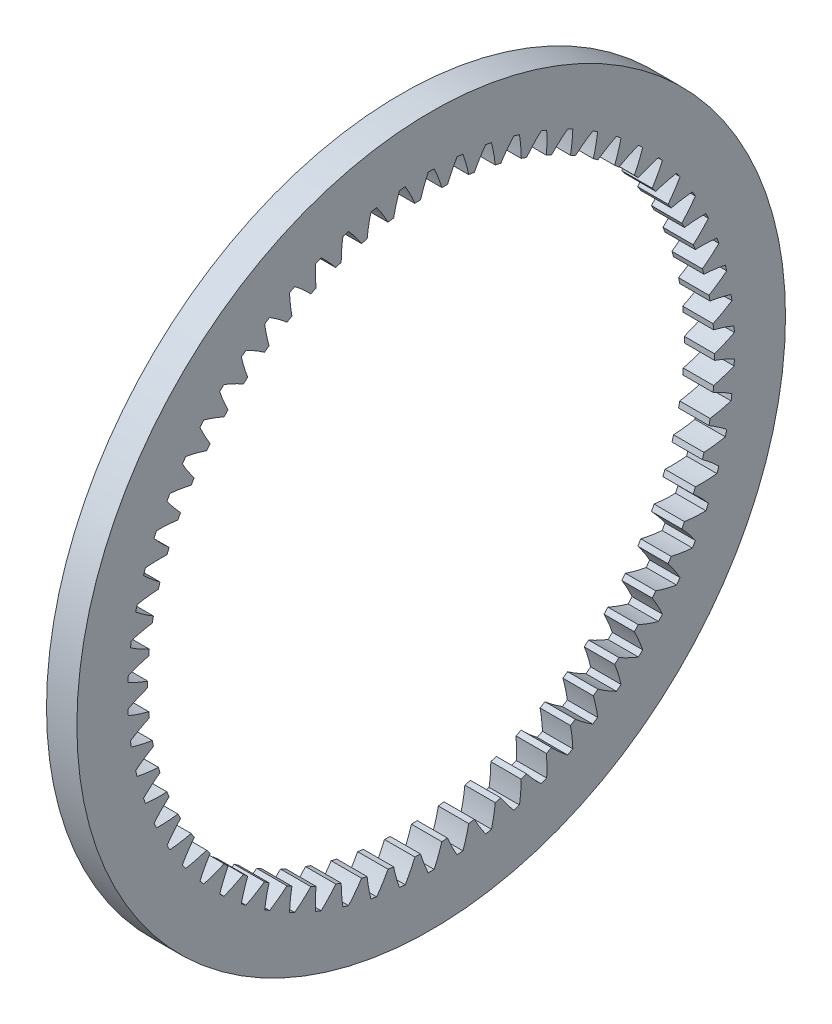
SolidWorks part; units mm, degrees
ref_plane "Plane1" through (0, 0, 0) normal (0, 0, 1) x (1, 0, 0)
ref_plane "Plane2" through (0, 0, 0) normal (0, 1, 0) x (1, 0, 0)
ref_plane "Plane3" through (0, 0, 0) normal (1, 0, 0) x (0, 0, -1)
other "Configuration Table"
sketch "HoldingSke" plane through (0, 0, 0) normal (0, 1, 0) x (1, 0, 0)
  line L0 (0, 0) -> (0.2324, -0.522)
  line L1 (-15, 0) -> (100, 0) construction
  line L2 (0, 0) -> (-2.1039, 2.3779)
  line L3 (0, 0) -> (-11.863, 4.5341)
  line L4 (0, 0) -> (3.5126, 7.8894)
  line L5 (0, 0) -> (-23.7986, -8.8762)
  line L6 (0, 0) -> (-10.5278, -7.1032)
  line L7 (-2.1039, 2.3779) -> (3.3635, 27.1825)
  line L8 (-76.2, 4.1279) -> (-54.61, 4.1279)
  line L9 (-71.009, 38.7566) -> (-53.1078, 45.2721)
  line L10 (-76.2, 71.12) -> (104.1128, 71.12)
  line L11 (0, 0) -> (-6, 0)
  line L12 (-76.2, 101.6) -> (-76.147, 101.6)
  line L13 (24.9733, 27.94) -> (52.9518, 28.4284)
  line L14 (24.9733, 27.94) -> (24.9743, 27.94)
  line L15 (24.9733, 27.94) -> (100.4006, 29.5858)
  circle A0 centre (0, 0) radius 70
  circle A1 centre (0, 0) radius 12.7
  circle A2 centre (0, 0) radius 12.7
  dimension "Num_teeth" = 66
  dimension "Pitch_radius" = 180.3128
  dimension "Width" = 6
  dimension "Diameter" = 140
sketch "BasProSke" plane through (0, 0, 0) normal (0, 1, 0) x (1, 0, 0)
  line L0 (-10, 0) -> (60, 0) construction
  line L1 (0, 56) -> (0, 70)
  line L2 (0, 56) -> (6, 56)
  line L3 (6, 56) -> (6, 70)
  line L4 (6, 70) -> (0, 70)
  dimension "Thickness" = 6
  dimension "Diameter" = 140
revolve "Base-Revolve" add sketch "BasProSke" angle 360 about L0
sketch "TooCutSke" plane through (0, 0, 0) normal (1, 0, 0) x (0, 0, -1)
  line L3 (1.5068, 57.7303) -> (1.5068, 53.6633) construction
  line L4 (0, 0) -> (0, 59.563) construction
  line L5 (0, 0) -> (-3.2512, 68.2501) construction
  line L6 (-25.562, 47.6782) -> (35.476, 50.5858) construction
  circle A0 centre (0, 0) radius 57.75 construction
  circle A1 centre (0, 0) radius 59.9385 construction
  circle A2 centre (0, 0) radius 48.8405 construction
  circle A3 centre (0, 0) radius 55.9746 construction
  arc A4 (2.1073, 55.9349) -> (0.5822, 59.9357) centre (-25.562, 47.6782) ccw
  arc A5 (2.1073, 55.9349) -> (-2.1073, 55.9349) centre (0, 0) ccw
  arc A6 (0.5822, 59.9357) -> (-0.5822, 59.9357) centre (0, 0) ccw
  arc A7 (-0.5822, 59.9357) -> (-2.1073, 55.9349) centre (25.562, 47.6782) ccw
extrude "ToothCut" cut sketch "TooCutSke" along normal through all
fillet "Breaks" [suppressed] radius 0.175
fillet "RootFillets" [suppressed] radius 0.4385
pattern_circular "TeethCuts" count 66 every 5.455 about axis through (-10, 0, 0) along (1, 0, 0) of "RootFillets", "Breaks", "ToothCut"
equation "' \"Module@HoldingSke\" = 6.35"
equation "' \"Num_teeth@HoldingSke\" = 24"
equation "' \"Ap@HoldingSke\" =  14.5"
equation "' \"Ap@HoldingSke\" = 14.5"
equation "' \"Width@HoldingSke\" = 12"
equation "' \"Diameter@HoldingSke\" = 8 * 25.4"
equation "' \"Show_teeth@HoldingSke\" = 100"
equation "' \"Backlash@HoldingSke\" = 0.009 * 25.4"
equation "' \"Addendum_fac@HoldingSke\" = 1.0"
equation "' \"Dedendum_fac@HoldingSke\" = 1.25"
equation "' \"Dedendum_add@HoldingSke\" = 0.00005 * 25.4"
equation "' \"Clearance_fac@HoldingSke\" = 0.25"
equation "\"Pitch@HoldingSke\" = 1 / \"Module@HoldingSke\" "
equation "\"Overcut_dia@TooCutSke\" = (\"Num_teeth@HoldingSke\" - 2 * \"Addendum_fac@HoldingSke\") / \"Pitch@HoldingSke\" - 0.002 * 25.4"
equation "\"Pitch_dia@TooCutSke\" = \"Num_teeth@HoldingSke\" / \"Pitch@HoldingSke\""
equation "\"Base_dia@TooCutSke\" = \"Num_teeth@HoldingSke\" / \"Pitch@HoldingSke\" * cos((\"Ap@HoldingSke\"  * 3.14159265 / 180)) * 0.90"
equation "\"Root_dia@TooCutSke\" = \"Num_teeth@HoldingSke\"  / \"Pitch@HoldingSke\" + 2 *  \"Dedendum_fac@HoldingSke\"/ \"Pitch@HoldingSke\" + \"Dedendum_add@HoldingSke\" * 2"
equation "\"Half_ang@TooCutSke\" = 180 / \"Num_teeth@HoldingSke\""
equation "\"Half_CT@TooCutSke\" = \"Num_teeth@HoldingSke\" / \"Pitch@HoldingSke\" * sin((3.14159265 / 2 / \"Num_teeth@HoldingSke\")) / 2 + 10 * \"Backlash@HoldingSke\" / 4"
equation "\"Flank_rad@TooCutSke\" = \"Num_teeth@HoldingSke\" / \"Pitch@HoldingSke\" / 4"
equation "\"Radius@RootFillets\"= \"Clearance_fac@HoldingSke\" / \"Pitch@HoldingSke\" + \"Dedendum_add@HoldingSke\""
equation "\"Break_rad@Breaks\" = 0.02 / \"Pitch@HoldingSke\" * 5"
equation "\"Num_teeth@TeethCuts\" = int( \"Show_teeth@HoldingSke\" ) + 1"
equation "\"Num_teeth@TeethCuts\" = ((sgn( \"Num_teeth@TeethCuts\" - \"Num_teeth@HoldingSke\" )-1)*( \"Num_teeth@TeethCuts\" - \"Num_teeth@HoldingSke\" ))/-2+ \"Num_teeth@HoldingSke\""
equation "\"Num_teeth@TeethCuts\" = ((sgn( \"Num_teeth@TeethCuts\" - 2.0)+1)*( \"Num_teeth@TeethCuts\" - 2.0))/2 +2.0"
equation "\"Angle@TeethCuts\" = 360.0 / \"Num_teeth@HoldingSke\""
equation "\"Diameter@BasProSke\" = \"Num_teeth@HoldingSke\"  / \"Pitch@HoldingSke\" + 2 *  \"Dedendum_fac@HoldingSke\"/ \"Pitch@HoldingSke\" + \"Dedendum_add@HoldingSke\" * 2 + 0.002 * 25.4"
equation "\"Diameter@BasProSke\" = ((sgn( \"Diameter@BasProSke\"  - \"Diameter@HoldingSke\" )+1)*( \"Diameter@BasProSke\"  - \"Diameter@HoldingSke\" ))/2 + \"Diameter@HoldingSke\""
equation "\"Inside_diameter@BasProSke\" =  (\"Num_teeth@HoldingSke\" - 2 * \"Addendum_fac@HoldingSke\") / \"Pitch@HoldingSke\" "
equation "\"Thickness@BasProSke\"  = \"Width@HoldingSke\""
